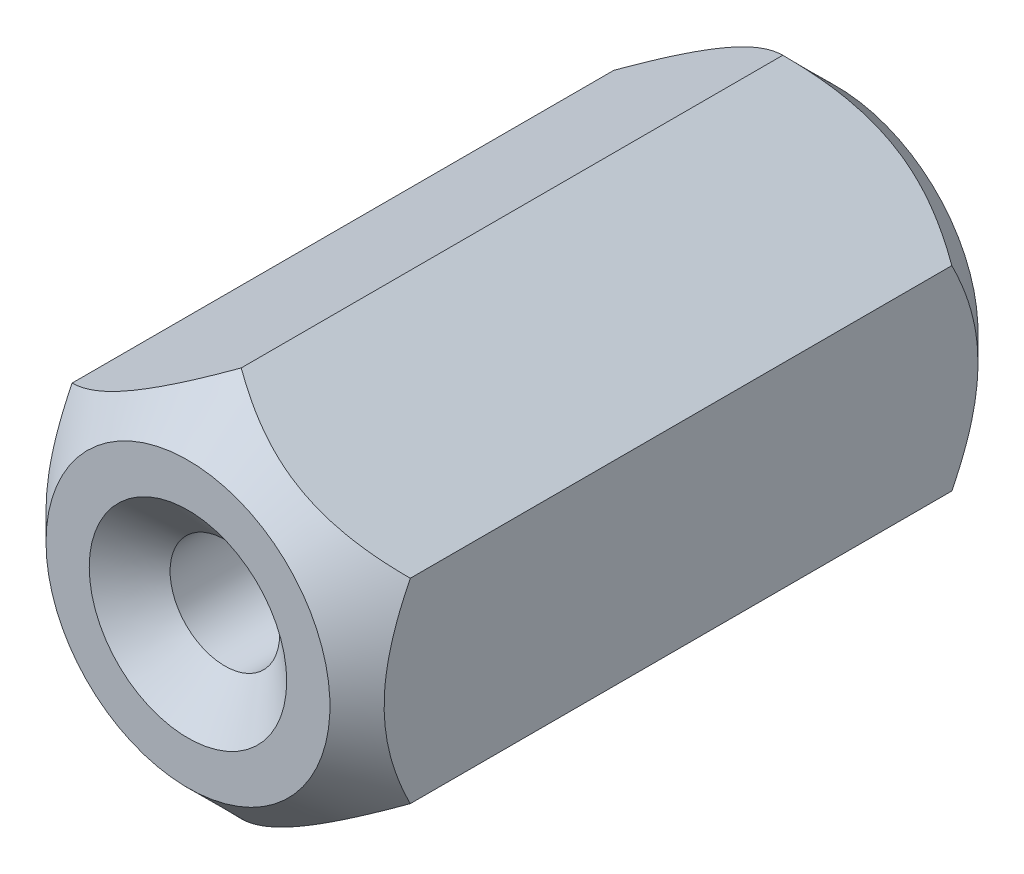
SolidWorks part; units mm, degrees
ref_plane "Front Plane" through (0, 0, 0) normal (0, 0, 1) x (1, 0, 0)
ref_plane "Top Plane" through (0, 0, 0) normal (0, 1, 0) x (1, 0, 0)
ref_plane "Right Plane" through (0, 0, 0) normal (1, 0, 0) x (0, 0, -1)
sketch "Sketch1" plane through (0, 0, 0) normal (0, 0, 1) x (1, 0, 0)
  line L1 (3.175, -1.8331) -> (3.175, 1.8331)
  line L2 (3.175, 1.8331) -> (0, 3.6662)
  line L3 (0, 3.6662) -> (-3.175, 1.8331)
  line L4 (-3.175, 1.8331) -> (-3.175, -1.8331)
  line L5 (-3.175, -1.8331) -> (0, -3.6662)
  line L6 (0, -3.6662) -> (3.175, -1.8331)
  circle A0 centre (0, 0) radius 3.175 construction
  dimension "D1" = 6.35
extrude "Boss-Extrude1" add sketch "Sketch1" along normal blind 6.085 and the other way blind 6.085
ref_axis "Axis1" through (0, 0, -0.635) along (0, 0, 1)
sketch "Sketch3" plane through (0, 0, 0) normal (1, 0, 0) x (0, 0, -1)
  line L0 (-6.085, 3.6662) -> (6.085, 3.6662) construction
  line L1 (-5.085, 3.6662) -> (-6.085, 2.6662)
  line L2 (-6.085, 1.8331) -> (-6.085, 3.6662) construction
  line L3 (-6.085, 2.6662) -> (-6.085, 3.6662)
  line L4 (-6.085, 3.6662) -> (-5.085, 3.6662)
  dimension "D1" = 1
  dimension "D2" = 45
revolve "Cut-Revolve2" cut sketch "Sketch3" angle 360 about axis through (0, 0, -0.635) along (0, 0, 1)
mirror "Mirror1" about plane through (0, 0, 0) normal (0, 0, 1) of "Cut-Revolve2"
hole_wizard "CSK for #1 Flat Head Machine Screw (100)1" positions "Sketch5" profile "Sketch4" countersink size "#1" standard "ANSI Inch" end condition through all
sketch "Sketch5" plane through (0, 0, 6.085) normal (0, 0, 1) x (1, 0, 0)
  point P0 (0, 0)
sketch "Sketch4" plane through (0, 0, 6.085) normal (1, 0, 0) x (0, -1, 0)
  line L0 (0, 0) -> (0, 12.17)
  line L1 (0, 12.17) -> (1.6637, 12.17)
  line L2 (1.0287, 11.535) -> (1.0287, 0.6927)
  line L3 (1.0287, 0.6927) -> (1.8542, 0)
  line L5 (1.8542, 0) -> (0, 0)
  line L6 (-1.0287, 0.6927) -> (-1.8542, 0) construction
  line L7 (1.6637, 12.17) -> (1.0287, 11.535)
  line L8 (-1.6637, 12.17) -> (-1.0287, 11.535) construction
  line L11 (0, -6.35) -> (0, 107.95) construction
  dimension "Thru Hole Dia." = 2.0574
  dimension "Thru Hole Depth" = 12.17
  dimension "Near C'Sink Dia." = 3.7084
  dimension "Near C'Sink Angle" = 100
  dimension "Far C'Sink Dia." = 3.3274
  dimension "Far C'Sink Angle" = 90
